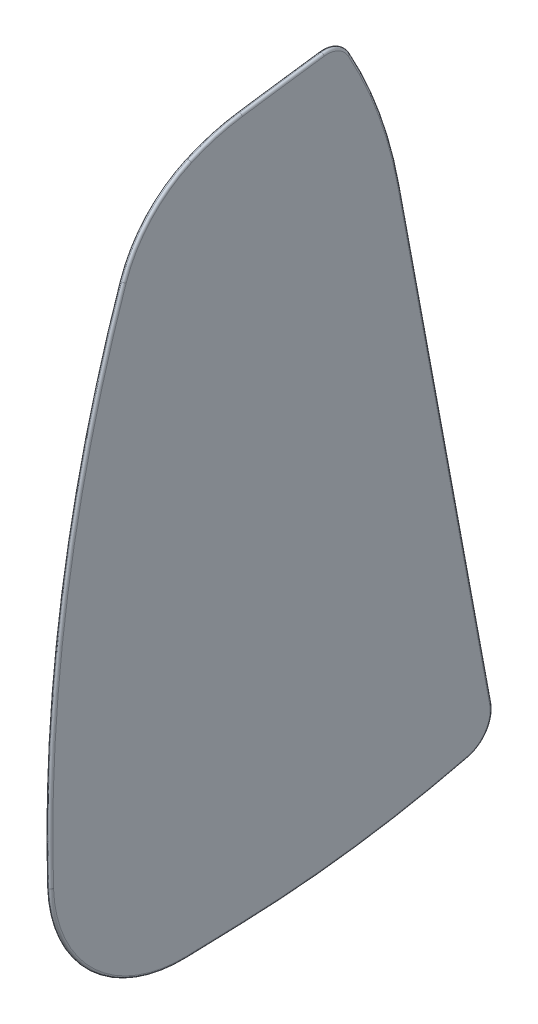
SolidWorks part; units mm, degrees
ref_plane "Front Plane" through (0, 0, 0) normal (0, 0, 1) x (1, 0, 0)
ref_plane "Top Plane" through (0, 0, 0) normal (0, 1, 0) x (1, 0, 0)
ref_plane "Right Plane" through (0, 0, 0) normal (1, 0, 0) x (0, 0, -1)
sketch "Sketch1" plane through (0, 0, 0) normal (1, 0, 0) x (0, 0, -1)
  line L0 (-47.664, 112.5507) -> (59.3261, 114.4182) construction
  line L1 (0, 228.6) -> (0, 0) construction
  line L2 (-17.9026, -0.5694) -> (0, 0)
  line L3 (51.4824, 183.0856) -> (81.395, 22.0458)
  arc A0 (0, 228.6) -> (-16.7579, 223.7831) centre (9.1043, 165.3677) ccw
  arc A1 (-38.4328, 200.1085) -> (-62.1369, 40.8842) centre (385.0599, 55.6857) ccw
  arc A2 (-16.7579, 223.7831) -> (-38.4328, 200.1085) centre (-0.558, 187.1921) ccw
  arc A3 (-62.1369, 40.8842) -> (-17.9026, -0.5694) centre (-19.2662, 42.3032) ccw
  arc A4 (0, 228.6) -> (26.6583, 232.3037) centre (387.5506, -2463.0609) cw
  arc A5 (26.6583, 232.3037) -> (35.3363, 227.9478) centre (27.8022, 223.7604) cw
  arc A6 (35.3363, 227.9478) -> (51.4824, 183.0856) centre (-94.0002, 156.0626) cw
  arc A7 (81.395, 22.0458) -> (73.7194, 10.1428) centre (71.2501, 20.1614) cw
  arc A8 (73.7194, 10.1428) -> (0, 0) centre (-11.2918, 355.0441) cw
  point P24 (69.9608, 9.238)
  point P25 (81.5698, 21.3365)
  point P26 (69.5733, 9.238)
  dimension "D1" = 228.6
extrude "Boss-Extrude1" add sketch "Sketch1" along normal blind 1.5875
fillet "Fillet1" radius 0.7937 22 edges at (0, 226.766, 8.5441) (0, 230.4849, -13.3246) (0, 231.464, -31.669) (0, 206.1713, -45.2282) (0, 102.5657, -66.4387) (0, 14.5695, -79.9219) (0, 3.1357, -37.1261) (0, -0.2847, 8.9513) (0, 11.0046, 48.5972) (0, 121.5711, 57.5044) (1.5875, 214.2142, 30.0731) (1.5875, 226.766, 8.5441) (1.5875, 230.4849, -13.3246) (1.5875, 231.464, -31.669) (1.5875, 206.1713, -45.2282) (1.5875, 102.5657, -66.4387) (1.5875, 14.5695, -79.9219) (1.5875, 3.1357, -37.1261) (1.5875, -0.2847, 8.9513) (1.5875, 11.0046, 48.5972) (0, 214.2142, 30.0731) (1.5875, 121.5711, 57.5044)
